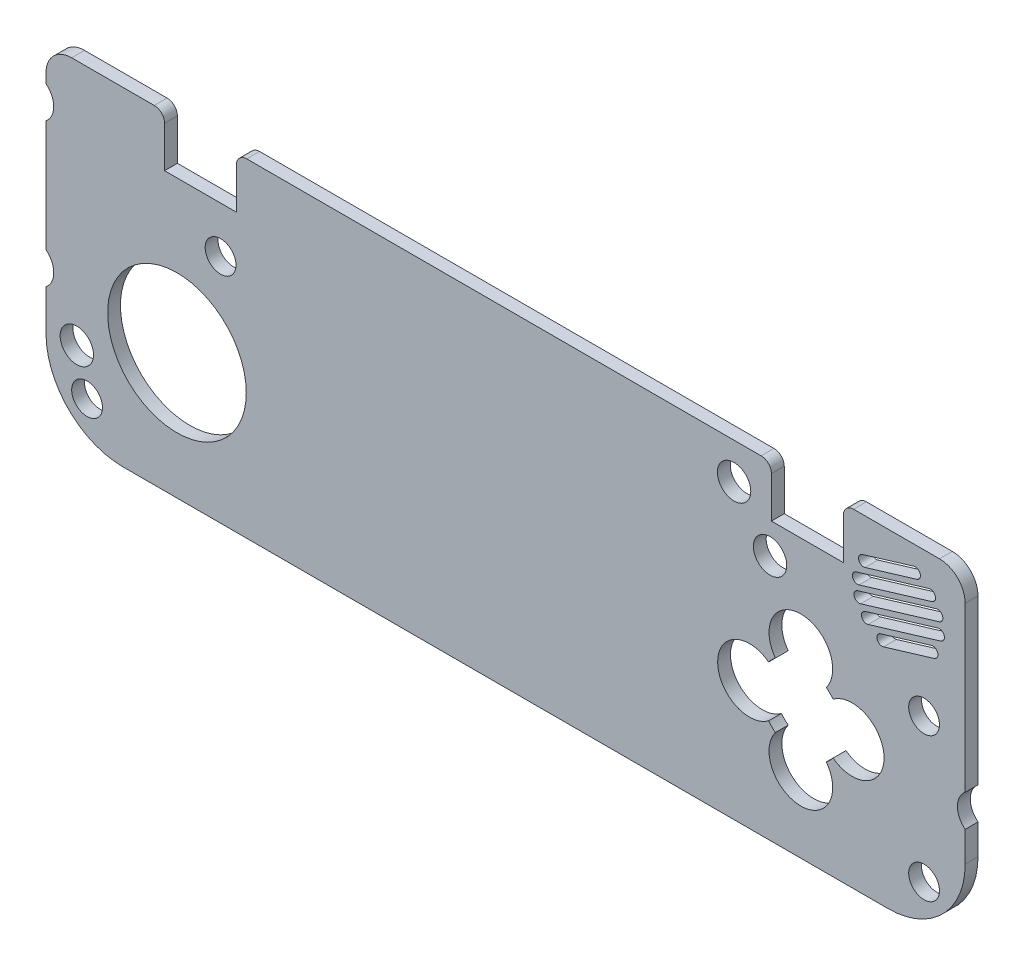
SolidWorks part; units mm, degrees
ref_plane "Plan de face" through (0, 0, 0) normal (0, 0, 1) x (1, 0, 0)
ref_plane "Plan de dessus" through (0, 0, 0) normal (0, 1, 0) x (1, 0, 0)
ref_plane "Plan de droite" through (0, 0, 0) normal (1, 0, 0) x (0, 0, -1)
sketch "Esquisse1" plane through (0, 0, 0) normal (0, 0, 1) x (1, 0, 0)
  line L1 (-89.2039, 33.3448) -> (79.7961, 33.3448)
  line L2 (-94.2039, 28.3448) -> (-94.2039, -15.6552)
  line L3 (-79.2039, -30.6552) -> (69.7961, -30.6552)
  line L4 (84.7961, 28.3448) -> (84.7961, -15.6552)
  arc A0 (-89.2039, 33.3448) -> (-94.2039, 28.3448) centre (-89.2039, 28.3448) ccw
  arc A1 (79.7961, 33.3448) -> (84.7961, 28.3448) centre (79.7961, 28.3448) cw
  arc A2 (69.7961, -30.6552) -> (84.7961, -15.6552) centre (69.7961, -15.6552) ccw
  arc A3 (-94.2039, -15.6552) -> (-79.2039, -30.6552) centre (-79.2039, -15.6552) ccw
  point P6 (-94.2039, 33.3448)
  point P9 (84.7961, 33.3448)
  point P12 (84.7961, -30.6552)
  dimension "D3" = 5
  dimension "D4" = 5
  dimension "D5" = 15
  dimension "D6" = 15
  dimension "D1" = 179
  dimension "D2" = 64
extrude "Boss.-Extru.1" add sketch "Esquisse1" along normal blind 2.5 contours L1 A1 L4 A2 L3 A3 L2 A0
sketch "12x12 Button" plane through (0, 0, 2.5) normal (0, 0, 1) x (1, 0, 0)
  line L0 (84.7961, 28.3448) -> (84.7961, -15.6552) construction
  line L1 (-79.2039, -30.6552) -> (69.7961, -30.6552) construction
  circle A0 centre (42.7961, -5.6552) radius 6.2
  circle A1 centre (52.7961, 4.3448) radius 6.2
  circle A2 centre (52.7961, -15.6552) radius 6.2
  circle A3 centre (62.7961, -5.6552) radius 6.2
  arc A5 (46.5181, -0.6967) -> (47.8376, 0.6228) centre (52.7961, -5.6552) cw
  arc A6 (59.0741, -0.6967) -> (57.7546, 0.6228) centre (52.7961, -5.6552) ccw
  arc A7 (59.0741, -10.6137) -> (57.7546, -11.9332) centre (52.7961, -5.6552) cw
  arc A9 (46.5181, -10.6137) -> (47.8376, -11.9332) centre (52.7961, -5.6552) ccw
  dimension "D1" = 22
  dimension "D2" = 32
  dimension "D3" = 42
  dimension "D4" = 32
  dimension "D5" = 15
  dimension "D6" = 35
  dimension "D7" = 25
  dimension "D8" = 25
sketch "Joystick" plane through (0, 0, 2.5) normal (0, 0, 1) x (1, 0, 0)
  line L0 (-79.2039, -30.6552) -> (69.7961, -30.6552) construction
  line L1 (-94.2039, 28.3448) -> (-94.2039, -15.6552) construction
  circle A0 centre (-68.7039, -6.1552) radius 13.5
  dimension "D1" = 24.5
  dimension "D2" = 25.5
extrude "Enlèv. mat.-Extru.2" cut sketch "Joystick" against normal blind 2.5
sketch "Esquisse2" plane through (0, 0, 2.5) normal (0, 0, 1) x (1, 0, 0)
  line L0 (-89.2039, 33.3448) -> (79.7961, 33.3448) construction
  line L1 (47.0661, 33.3448) -> (61.0661, 33.3448)
  line L2 (47.0661, 33.3448) -> (47.0661, 23.3448)
  line L3 (47.0661, 23.3448) -> (61.0661, 23.3448)
  line L4 (61.0661, 33.3448) -> (61.0661, 23.3448)
  line L5 (84.7961, 28.3448) -> (84.7961, -15.6552) construction
  dimension "D1" = 23.73
  dimension "D2" = 14
extrude "Enlèv. mat.-Extru.3" cut sketch "Esquisse2" against normal blind 10
fillet "Congé1" radius 2 1 edges at (47.0661, 33.3448, 1.25)
fillet "Congé2" radius 2 1 edges at (61.0661, 33.3448, 1.25)
sketch "Esquisse3" plane through (0, 0, 2.5) normal (0, 0, 1) x (1, 0, 0)
  line L0 (-89.2039, 33.3448) -> (45.0661, 33.3448) construction
  line L1 (-71.1139, 33.3448) -> (-57.1139, 33.3448)
  line L2 (-71.1139, 33.3448) -> (-71.1139, 23.3448)
  line L3 (-71.1139, 23.3448) -> (-57.1139, 23.3448)
  line L4 (-57.1139, 33.3448) -> (-57.1139, 23.3448)
  line L5 (-94.2039, 28.3448) -> (-94.2039, -15.6552) construction
  dimension "D1" = 23.09
  dimension "D2" = 10
  dimension "D3" = 14
extrude "Enlèv. mat.-Extru.4" cut sketch "Esquisse3" against normal blind 10 contours L2 L1 L4 L3
fillet "Congé3" radius 2 1 edges at (-71.1139, 33.3448, 1.25)
fillet "Congé4" radius 2 1 edges at (-57.1139, 33.3448, 1.25)
extrude "Enlèv. mat.-Extru.5" cut sketch "12x12 Button" against normal blind 10 contours A0 A9 A2 A7 A3 A6 A1 A5 | A0 | A1 | A3 | A2 region at (42.7961, -5.6552, 2.5) region at (52.7961, -5.6552, 2.5) region at (52.7961, 4.3448, 2.5) region at (52.7961, -15.6552, 2.5) region at (62.7961, -5.6552, 2.5)
sketch "Esquisse4" plane through (0, 0, 2.5) normal (0, 0, 1) x (1, 0, 0)
  line L0 (84.7961, 28.3448) -> (84.7961, -15.6552) construction
  line L1 (64.137, 19.0344) -> (79.4552, 23.6552) construction
  line L2 (63.0661, 33.3448) -> (79.7961, 33.3448) construction
  line L3 (63.8482, 19.9918) -> (79.1664, 24.6126)
  line L4 (64.4258, 18.077) -> (79.744, 22.6978)
  line L5 (63.8286, 22.0649) -> (78.0363, 26.3507) construction
  line L6 (63.5398, 23.0223) -> (77.7475, 27.3081)
  line L7 (64.1174, 21.1075) -> (78.3251, 25.3933)
  line L8 (65.0217, 25.6002) -> (75.0872, 28.6364) construction
  line L9 (64.7329, 26.5575) -> (74.7984, 29.5938)
  line L10 (65.3105, 24.6428) -> (75.376, 27.6791)
  line L11 (65.6035, 16.28) -> (79.7564, 20.5493) construction
  line L12 (65.3147, 17.2374) -> (79.4676, 21.5066)
  line L13 (65.8923, 15.3226) -> (80.0452, 19.5919)
  line L14 (68.6116, 14.0059) -> (78.5077, 16.9911) construction
  line L15 (68.3228, 14.9633) -> (78.2189, 17.9485)
  line L16 (68.9004, 13.0485) -> (78.7965, 16.0337)
  circle A0 centre (71.7961, 21.3448) radius 10
  circle A1 centre (71.7961, 21.3448) radius 8
  arc A2 (63.8482, 19.9918) -> (64.4258, 18.077) centre (64.137, 19.0344) ccw
  arc A3 (79.744, 22.6978) -> (79.1664, 24.6126) centre (79.4552, 23.6552) ccw
  arc A4 (63.5398, 23.0223) -> (64.1174, 21.1075) centre (63.8286, 22.0649) ccw
  arc A5 (78.3251, 25.3933) -> (77.7475, 27.3081) centre (78.0363, 26.3507) ccw
  arc A6 (64.7329, 26.5575) -> (65.3105, 24.6428) centre (65.0217, 25.6002) ccw
  arc A7 (75.376, 27.6791) -> (74.7984, 29.5938) centre (75.0872, 28.6364) ccw
  arc A8 (65.3147, 17.2374) -> (65.8923, 15.3226) centre (65.6035, 16.28) ccw
  arc A9 (80.0452, 19.5919) -> (79.4676, 21.5066) centre (79.7564, 20.5493) ccw
  arc A10 (68.3228, 14.9633) -> (68.9004, 13.0485) centre (68.6116, 14.0059) ccw
  arc A11 (78.7965, 16.0337) -> (78.2189, 17.9485) centre (78.5077, 16.9911) ccw
  point P9 (71.7961, 21.3448)
  point P16 (70.9324, 24.2078)
  point P25 (70.0545, 27.1183)
  point P36 (72.68, 18.4146)
  point P47 (73.5596, 15.4985)
  dimension "D1" = 13
  dimension "D2" = 12
  dimension "D4" = 0
  dimension "D5" = 1.04
  dimension "D6" = 360
  dimension "D7" = 360
  dimension "D8" = 1.0459
extrude "Enlèv. mat.-Extru.8" cut sketch "Esquisse4" against normal blind 10 contours L4 A1 L3 | L3 A2 A0 L4 A1 | L6 A4 A0 A1 | L9 A6 A0 A1 | L10 A7 A1 L9 A6 | A1 A9 L12 A8 L13 | A1 A8 A0 L13 | A1 A10 A0 L16 | A1 A11 L15 A10 L16 | L16 A11 A0 A1 | A0 A9 A1 L13 | A0 A3 L3 A1 L4 | A0 A5 L6 A1 | L7 A5 A1 L6 A4 | A0 A7 L9 A1 region at (63.7416, 18.9151, 2.5) region at (71.7961, 21.3448, 2.5) region at (79.8505, 23.7744, 2.5) region at (63.4219, 22.1121, 2.5) region at (70.9376, 24.1907, 2.5) region at (78.349, 26.6149, 2.5) region at (72.6746, 18.4323, 2.5) region at (65.294, 16.0125, 2.5) region at (80.1623, 20.4975, 2.5) region at (64.7771, 25.9214, 2.5) region at (70.0739, 27.0538, 2.5) region at (75.1134, 29.0394, 2.5) region at (73.5392, 15.5661, 2.5) region at (68.602, 13.6004, 2.5) region at (78.7399, 16.6585, 2.5)
sketch "Esquisse5" plane through (0, 0, 2.5) normal (0, 0, 1) x (1, 0, 0)
  line L0 (84.7961, 28.3448) -> (84.7961, -15.6552) construction
  line L1 (-79.2039, -30.6552) -> (69.7961, -30.6552) construction
  line L2 (-94.2039, 28.3448) -> (-94.2039, -15.6552) construction
  line L7 (63.0661, 33.3448) -> (79.7961, 33.3448) construction
  line L8 (-55.1139, 33.3448) -> (45.0661, 33.3448) construction
  circle A0 centre (76.7961, -22.6552) radius 3
  circle A1 centre (-86.2039, -22.6552) radius 3
  circle A2 centre (76.7961, 5.3448) radius 3
  circle A3 centre (-60.2039, 14.3448) radius 3
  circle A4 centre (-88.2039, -14.6552) radius 3.25
  circle A5 centre (39.7961, 26.3448) radius 3.25
  circle A6 centre (46.7961, 17.3448) radius 3.25
  dimension "D1" = 8
  dimension "D3" = 8
  dimension "D5" = 8
  dimension "D7" = 19
  dimension "D9" = 6
  dimension "D11" = 7
  dimension "D13" = 38
  dimension "D2" = 8
  dimension "D4" = 8
  dimension "D6" = 28
  dimension "D8" = 34
  dimension "D10" = 16
  dimension "D12" = 45
  dimension "D14" = 16
extrude "Enlèv. mat.-Extru.9" cut sketch "Esquisse5" against normal blind 10
sketch "Esquisse6" plane through (0, 0, 2.5) normal (0, 0, 1) x (1, 0, 0)
  line L0 (-76.1808, -30.6552) -> (-76.1808, -4.6552)
  line L1 (-79.2039, -30.6552) -> (69.7961, -30.6552) construction
  line L2 (-76.1808, -4.6552) -> (-94.2039, -4.6552)
  line L3 (-94.2039, 28.3448) -> (-94.2039, -15.6552) construction
  line L4 (-94.2039, -4.6552) -> (-99.2039, -4.6552)
  line L5 (-81.1589, 33.3448) -> (-81.1589, 23.3448)
  line L6 (-89.2039, 33.3448) -> (-73.1139, 33.3448) construction
  line L7 (-81.1589, 23.3448) -> (-94.2039, 23.3448)
  line L8 (-94.2039, 23.3448) -> (-99.2039, 23.3448)
  line L9 (68.4263, -30.6552) -> (68.4263, -6.6552)
  line L10 (68.4263, -6.6552) -> (84.7961, -6.6552)
  line L11 (84.7961, 28.3448) -> (84.7961, -15.6552) construction
  line L12 (84.7961, -6.6552) -> (89.7961, -6.6552)
  circle A0 centre (-96.7039, -4.6552) radius 4
  circle A1 centre (-96.7039, 23.3448) radius 4
  circle A2 centre (87.2961, -6.6552) radius 4
extrude "Enlèv. mat.-Extru.11" cut sketch "Esquisse6" against normal blind 10
